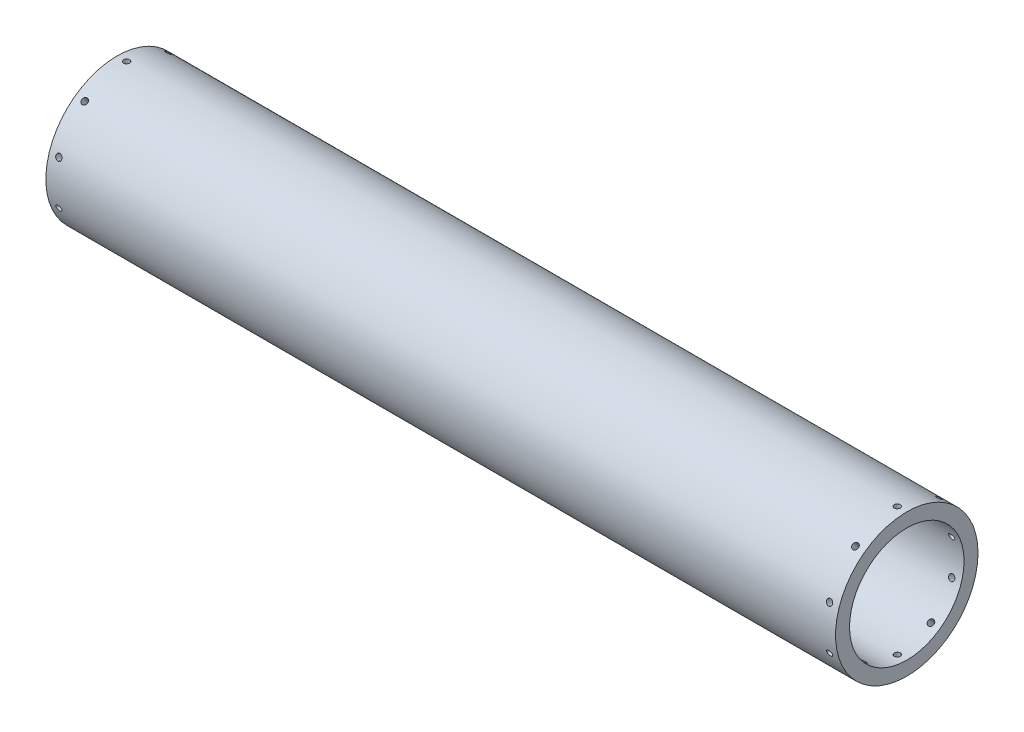
SolidWorks part; units mm, degrees
material "7075-T6 (SN)"
ref_plane "Front Plane" through (0, 0, 0) normal (0, 0, 1) x (1, 0, 0)
ref_plane "Top Plane" through (0, 0, 0) normal (0, 1, 0) x (1, 0, 0)
ref_plane "Right Plane" through (0, 0, 0) normal (1, 0, 0) x (0, 0, -1)
sketch "Sketch1" plane through (0, 0, 0) normal (1, 0, 0) x (0, 0, -1)
  circle A0 centre (0, 0) radius 45.9486
  circle A1 centre (0, 0) radius 57.15
  dimension "D1" = 91.8972
  dimension "D2" = 114.3
extrude "Boss-Extrude1" add sketch "Sketch1" along normal blind 633.73
sketch "Sketch2" plane through (0, 0, 0) normal (-1, 0, 0) x (0, 0, 1)
  circle A0 centre (0, 0) radius 44.577
  circle A1 centre (0, 0) radius 45.9486
  dimension "D1" = 89.154
extrude "Boss-Extrude2" add sketch "Sketch2" against normal blind 88.9
sketch "Sketch4" plane through (0, 0, 0) normal (0, 0, 1) x (1, 0, 0)
  line L0 (0, 0) -> (0, 88.0135) construction
  line L1 (0, 57.15) -> (0, -57.15) construction
  line L2 (0, -55) -> (0, 55) construction
ref_plane "Plane1" through (0, 57.15, 0) normal (0, 1, 0) x (1, 0, 0)
sketch "Sketch6" plane through (0, 57.15, 0) normal (0, 1, 0) x (1, 0, 0)
  line L0 (0, 57.15) -> (0, -57.15) construction
  circle A0 centre (7.62, 0) radius 2.413
  dimension "D1" = 4.826
  dimension "D2" = 7.62
extrude "Cut-Extrude1" cut sketch "Sketch6" against normal blind 15.24
pattern_circular "CirPattern1" count 10 every 36 about axis through (0, 0, 0) along (-1, 0, 0) of "Cut-Extrude1"
sketch "Sketch7" plane through (0, 57.15, 0) normal (0, 1, 0) x (1, 0, 0)
  line L0 (633.73, -57.15) -> (633.73, 57.15) construction
  circle A0 centre (626.11, 0) radius 2.413
  dimension "D2" = 4.826
  dimension "D1" = 7.62
extrude "Cut-Extrude2" cut sketch "Sketch7" against normal blind 15.24
pattern_circular "CirPattern2" count 10 every 36 about axis through (633.73, 0, 0) along (1, 0, 0) of "Cut-Extrude2"
